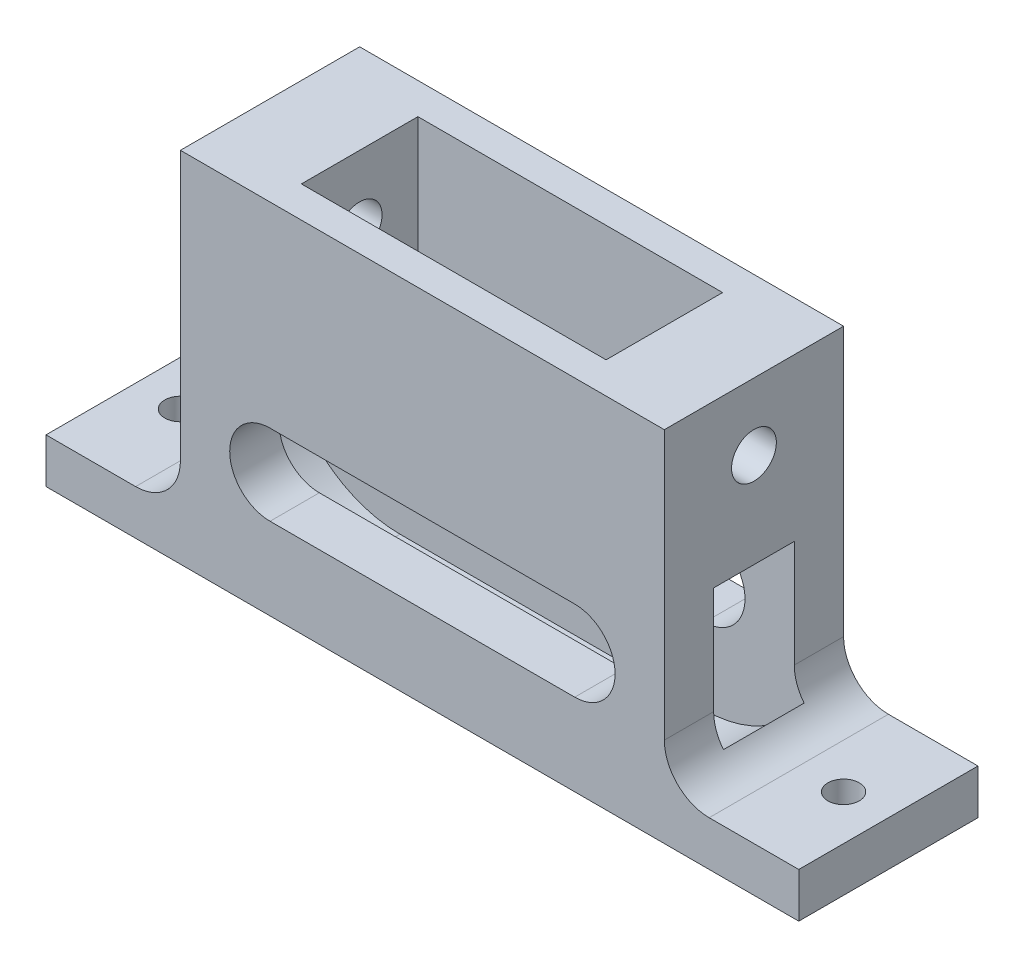
SolidWorks part; units mm, degrees
ref_plane "Front Plane" through (0, 0, 0) normal (0, 0, 1) x (1, 0, 0)
ref_plane "Top Plane" through (0, 0, 0) normal (0, 1, 0) x (1, 0, 0)
ref_plane "Right Plane" through (0, 0, 0) normal (1, 0, 0) x (0, 0, -1)
sketch "Sketch1" plane through (0, 0, 0) normal (0, 1, 0) x (1, 0, 0)
  line L1 (-27, 10) -> (27, 10)
  line L2 (-27, 10) -> (-27, -10)
  line L3 (-27, -10) -> (27, -10)
  line L4 (27, 10) -> (27, -10)
  line L5 (-27, 10) -> (27, -10) construction
  line L6 (-27, -10) -> (27, 10) construction
  point P0 (0, 0)
  dimension "D1" = 20
  dimension "D2" = 54
extrude "Boss-Extrude1" add sketch "Sketch1" along normal blind 40
sketch "Sketch4" plane through (0, 0, 0) normal (0, -1, 0) x (1, 0, 0)
  line L0 (27, -10) -> (-27, -10) construction
  line L1 (-27, 10) -> (-42, 10)
  line L2 (-27, 10) -> (-27, -10)
  line L3 (-27, -10) -> (-42, -10)
  line L4 (-42, 10) -> (-42, -10)
  line L5 (0, -55) -> (0, 55) construction
  line L6 (42, 10) -> (42, -10)
  line L7 (27, -10) -> (42, -10)
  line L8 (27, 10) -> (27, -10)
  line L9 (27, 10) -> (42, 10)
  dimension "D1" = 15
extrude "Boss-Extrude2" add sketch "Sketch4" against normal blind 5
fillet "Fillet1" radius 5 2 edges at (27, 5, 0) (-27, 5, 0)
sketch "Sketch6" plane through (0, 40, 0) normal (0, -1, 0) x (1, 0, 0)
  line L0 (17, 6.5) -> (-17, -6.5) construction
  line L1 (-17, 6.5) -> (17, 6.5)
  line L2 (-17, 6.5) -> (-17, -6.5)
  line L3 (-17, -6.5) -> (17, -6.5)
  line L4 (17, 6.5) -> (17, -6.5)
  line L5 (-27, -10) -> (-27, 10) construction
  dimension "D1" = 10
  dimension "D2" = 13
extrude "Cut-Extrude3" cut sketch "Sketch6" along normal offset from surface (26.35 mm away) 13.65 up to face at (0, 0, 0)
sketch "Sketch7" plane through (0, 0, 10) normal (0, 0, 1) x (1, 0, 0)
  line L0 (-17, 13.65) -> (17, 13.65) construction
  line L4 (-17, 18.15) -> (17, 18.15)
  line L8 (-17, 9.15) -> (17, 9.15)
  line L9 (0, 0) -> (0, 40) construction
  line L10 (-27, 40) -> (27, 40) construction
  line L11 (-17, 13.65) -> (-17, 40) construction
  line L12 (-42, 0) -> (42, 0) construction
  arc A2 (-17, 18.15) -> (-17, 9.15) centre (-17, 13.65) ccw
  arc A3 (17, 9.15) -> (17, 18.15) centre (17, 13.65) ccw
  point P2 (0, 13.65)
  dimension "D1" = 9
  dimension "D2" = 13.65
extrude "Cut-Extrude4" cut sketch "Sketch7" against normal through all
sketch "Sketch3" plane through (-27, 0, 0) normal (-1, 0, 0) x (0, 0, 1)
  line L2 (-10, 32.52) -> (10, 32.52) construction
  line L3 (-10, 40) -> (-10, 10) construction
  line L4 (10, 40) -> (10, 10) construction
  line L6 (10, 0) -> (-10, 0) construction
  line L7 (-10, 40) -> (-10, 10) construction
  line L8 (-10, 13.65) -> (-10, 32.52) construction
  circle A0 centre (0, 32.52) radius 2.5
  dimension "D1" = 5
  dimension "D2" = 13.65
  dimension "D3" = 18.87
extrude "Cut-Extrude2" cut sketch "Sketch3" against normal through all
ref_plane "Plane2" through (0, 0, -4.5) normal (0, 0, -1) x (-1, 0, 0)
sketch "Sketch8" plane through (0, 0, -4.5) normal (0, 0, -1) x (-1, 0, 0)
  line L0 (-17, 13.65) -> (17, 13.65) construction
  line L1 (-17, 26.65) -> (17, 26.65)
  line L2 (-17, 0.65) -> (17, 0.65)
  arc A1 (-17, 26.65) -> (-17, 0.65) centre (-17, 13.65) ccw
  arc A2 (17, 0.65) -> (17, 26.65) centre (17, 13.65) ccw
  point P3 (0, 13.65)
  dimension "D1" = 13
extrude "Cut-Extrude5" cut sketch "Sketch8" against normal blind 9
sketch "Sketch9" plane through (0, 5, 0) normal (0, 1, 0) x (1, 0, 0)
  line L0 (-32, 0) -> (-42, 0) construction
  line L1 (-32, -10) -> (-32, 10) construction
  line L2 (-42, -10) -> (-42, 10) construction
  line L3 (32, 0) -> (42, 0) construction
  line L4 (32, 10) -> (32, -10) construction
  line L5 (42, 10) -> (42, -10) construction
  circle A0 centre (-37, 0) radius 1.75
  circle A1 centre (37, 0) radius 1.75
  dimension "D1" = 3.5
  dimension "D2" = 3.5
extrude "Cut-Extrude6" cut sketch "Sketch9" against normal through all
